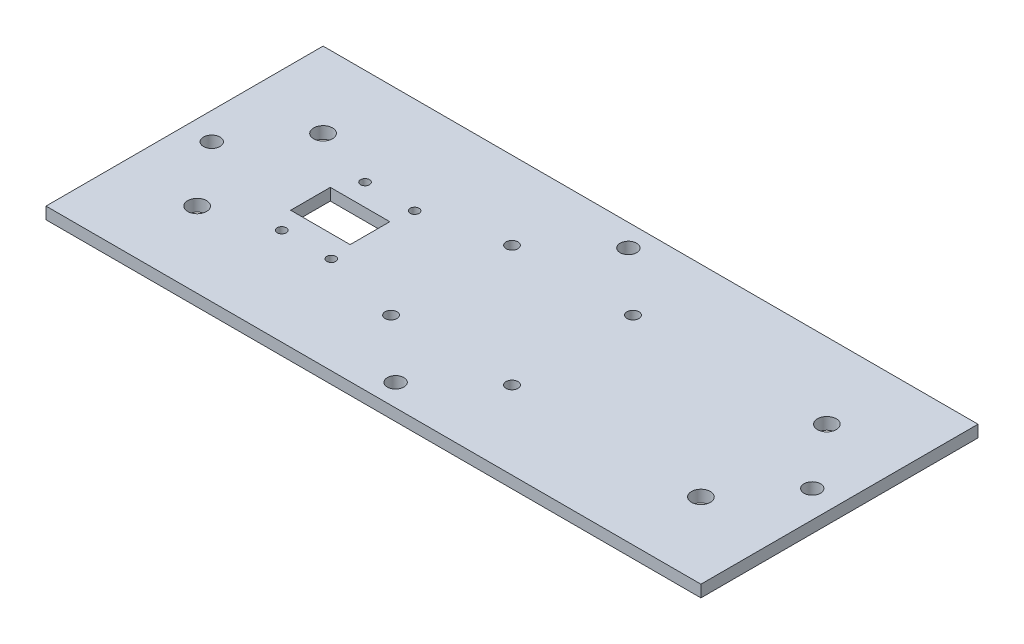
SolidWorks part; units mm, degrees
material "Thornel VCB-20 Carbon Cloth"
ref_plane "Front Plane" through (0, 0, 0) normal (0, 0, 1) x (1, 0, 0)
ref_plane "Top Plane" through (0, 0, 0) normal (0, 1, 0) x (1, 0, 0)
ref_plane "Right Plane" through (0, 0, 0) normal (1, 0, 0) x (0, 0, -1)
sketch "Sketch1" plane through (0, 0, 0) normal (0, 1, 0) x (1, 0, 0)
  line L0 (82.55, -34.925) -> (82.55, 34.925)
  line L1 (82.55, -34.925) -> (-82.55, -34.925)
  line L2 (82.55, 34.925) -> (-82.55, 34.925)
  line L3 (-82.55, -34.925) -> (-82.55, 34.925)
  line L4 (82.55, -34.925) -> (-82.55, 34.925) construction
  line L5 (82.55, 34.925) -> (-82.55, -34.925) construction
  point P1 (0, 0)
  dimension "D1" = 165.1
  dimension "D2" = 69.85
extrude "Boss-Extrude1" add sketch "Sketch1" along normal blind 3
sketch "Sketch6" plane through (0, 0, 0) normal (0, -1, 0) x (1, 0, 0)
  line L0 (-82.55, -34.925) -> (-82.55, 34.925) construction
  line L1 (-50.8, 5) -> (-35.8, 5)
  line L2 (-50.8, 5) -> (-50.8, -5)
  line L3 (-50.8, -5) -> (-35.8, -5)
  line L4 (-35.8, 5) -> (-35.8, -5)
  circle A0 centre (-15.25, 15.25) radius 1.5
  circle A1 centre (15.25, 15.25) radius 1.5
  circle A2 centre (-15.25, -15.25) radius 1.5
  circle A3 centre (15.25, -15.25) radius 1.5
  point P8 (-35.8, 0)
  point P9 (0, 0)
  dimension "D5" = 3
  dimension "D6" = 3
  dimension "D7" = 3
  dimension "D8" = 3
  dimension "D1" = 15
  dimension "D2" = 10
  dimension "D3" = 31.75
  dimension "D9" = 15.25
  dimension "D10" = 15.25
  dimension "D11" = 15.25
  dimension "D12" = 15.25
  dimension "D13" = 15.25
  dimension "D14" = 15.25
  dimension "D15" = 15.25
  dimension "D16" = 15.25
extrude "Cut-Extrude1" cut sketch "Sketch6" against normal up to next
sketch "Sketch7" plane through (0, 3, 0) normal (0, 1, 0) x (1, 0, 0)
  line L0 (-82.55, 34.925) -> (-82.55, -34.925) construction
  line L1 (82.55, -34.925) -> (82.55, 34.925) construction
  line L2 (-82.55, -34.925) -> (82.55, -34.925) construction
  line L3 (82.55, 34.925) -> (-82.55, 34.925) construction
  circle A0 centre (-77.47, 29.845) radius 1.5
  circle A1 centre (-77.47, -29.845) radius 1.5
  circle A2 centre (77.47, -29.845) radius 1.5
  circle A3 centre (77.47, 29.845) radius 1.5
  dimension "D9" = 3
  dimension "D10" = 3
  dimension "D11" = 3
  dimension "D12" = 3
  dimension "D1" = 5.08
  dimension "D2" = 5.08
  dimension "D3" = 5.08
  dimension "D4" = 5.08
  dimension "D5" = 5.08
  dimension "D6" = 5.08
  dimension "D7" = 5.08
  dimension "D8" = 5.08
sketch "Sketch8" plane through (0, 3, 0) normal (0, 1, 0) x (1, 0, 0)
  line L0 (-82.55, -34.925) -> (82.55, -34.925) construction
  line L1 (-82.55, 34.925) -> (-82.55, -34.925) construction
  line L2 (82.55, -34.925) -> (82.55, 34.925) construction
  line L3 (82.55, 34.925) -> (-82.55, 34.925) construction
  circle A0 centre (-63.5, -15.875) radius 2.3813
  circle A1 centre (-63.5, 15.875) radius 2.3813
  circle A2 centre (63.5, 15.875) radius 2.3813
  circle A3 centre (63.5, -15.875) radius 2.3813
  dimension "D1" = 4.7625
  dimension "D4" = 4.7625
  dimension "D5" = 4.7625
  dimension "D6" = 4.7625
  dimension "D2" = 19.05
  dimension "D3" = 19.05
  dimension "D7" = 19.05
  dimension "D8" = 19.05
  dimension "D9" = 19.05
  dimension "D10" = 19.05
  dimension "D11" = 19.05
  dimension "D12" = 19.05
extrude "Cut-Extrude3" cut sketch "Sketch8" against normal up to next
sketch "Sketch9" plane through (0, 3, 0) normal (0, 1, 0) x (1, 0, 0)
  line L0 (-82.55, 34.925) -> (-82.55, -34.925) construction
  line L1 (82.55, -34.925) -> (82.55, 34.925) construction
  circle A0 centre (-75.692, 0) radius 2.0828
  circle A1 centre (75.692, 0) radius 2.0828
  dimension "D1" = 6.858
  dimension "D2" = 6.858
extrude "Cut-Extrude5" cut sketch "Sketch9" against normal blind 5.08
sketch "Sketch10" plane through (0, 3, 0) normal (0, 1, 0) x (1, 0, 0)
  line L0 (-82.55, -34.925) -> (82.55, -34.925) construction
  line L1 (82.55, 34.925) -> (-82.55, 34.925) construction
  circle A0 centre (0, -29.337) radius 2.0828
  circle A1 centre (0, 29.337) radius 2.0828
  dimension "D1" = 5.588
  dimension "D2" = 5.588
extrude "Cut-Extrude6" cut sketch "Sketch10" against normal blind 5.08 contours A1 | A0
sketch "Sketch11" plane through (0, 3, 0) normal (0, 1, 0) x (1, 0, 0)
  line L1 (-35.05, 10.5) -> (-47.55, 10.5) construction
  line L2 (-35.05, 10.5) -> (-35.05, -10.5) construction
  line L3 (-35.05, -10.5) -> (-47.55, -10.5) construction
  line L4 (-47.55, 10.5) -> (-47.55, -10.5) construction
  line L5 (-35.05, 10.5) -> (-47.55, -10.5) construction
  line L6 (-35.05, -10.5) -> (-47.55, 10.5) construction
  line L7 (-35.8, 5) -> (-50.8, 5) construction
  circle A0 centre (-47.55, 10.5) radius 1.125
  circle A1 centre (-35.05, 10.5) radius 1.125
  circle A2 centre (-35.05, -10.5) radius 1.125
  circle A3 centre (-47.55, -10.5) radius 1.125
  point P0 (-41.3, 0)
  point P9 (-43.3, 5)
  point P11 (-35.4401, 10.5)
  point P13 (-35.3929, -10.5)
  point P15 (-47.1956, -10.5)
  dimension "D4" = 2.25
  dimension "D5" = 2.25
  dimension "D6" = 2.25
  dimension "D7" = 2.25
  dimension "D1" = 12.5
  dimension "D2" = 21
  dimension "D3" = 2
extrude "Cut-Extrude7" cut sketch "Sketch11" against normal blind 41.91
